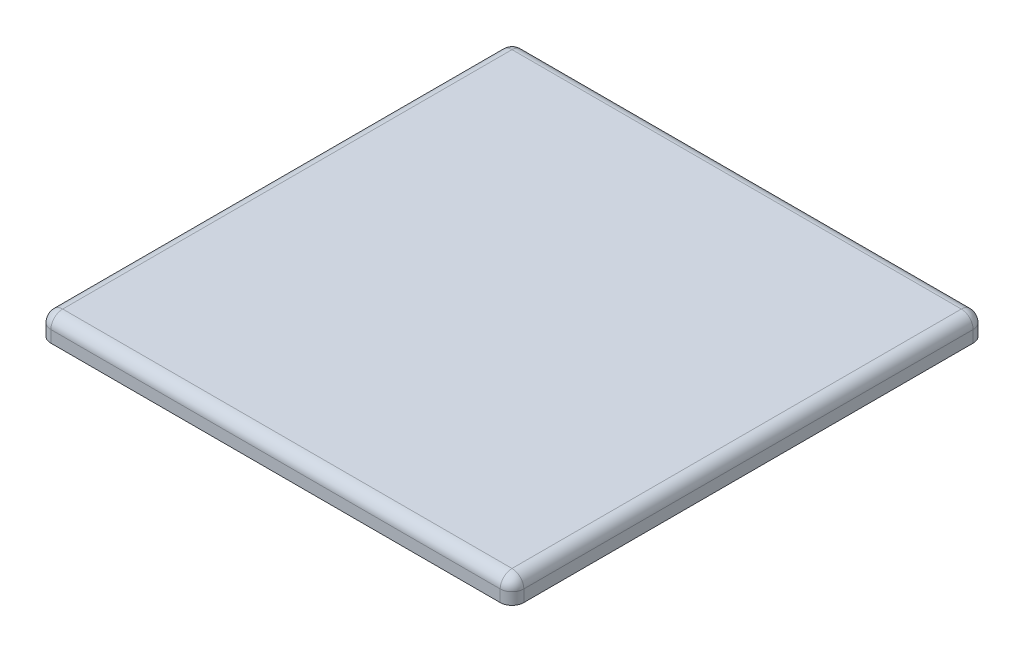
SolidWorks part; units mm, degrees
material "Polyurethane Foam Flexible"
ref_plane "Front Plane" through (0, 0, 0) normal (0, 0, 1) x (1, 0, 0)
ref_plane "Top Plane" through (0, 0, 0) normal (0, 1, 0) x (1, 0, 0)
ref_plane "Right Plane" through (0, 0, 0) normal (1, 0, 0) x (0, 0, -1)
sketch "Sketch1" plane through (0, 0, 0) normal (0, 1, 0) x (1, 0, 0)
  line L1 (-254, 254) -> (254, 254)
  line L2 (-254, 254) -> (-254, -254)
  line L3 (-254, -254) -> (254, -254)
  line L4 (254, 254) -> (254, -254)
  line L5 (-254, 254) -> (254, -254) construction
  line L6 (-254, -254) -> (254, 254) construction
  point P0 (0, 0)
  dimension "D1" = 508
  dimension "D2" = 508
extrude "Boss-Extrude1" add sketch "Sketch1" along normal blind 25.4
fillet "Fillet1" radius 12.7 4 edges at (0, 25.4, -254) (-254, 25.4, 0) (0, 25.4, 254) (254, 25.4, 0)
fillet "Fillet2" radius 12.7 8 edges at (-254, 6.35, -254) (-250.2803, 21.6803, -250.2803) (250.2803, 21.6803, -250.2803) (254, 6.35, -254) (254, 6.35, 254) (250.2803, 21.6803, 250.2803) (-254, 6.35, 254) (-250.2803, 21.6803, 250.2803)
